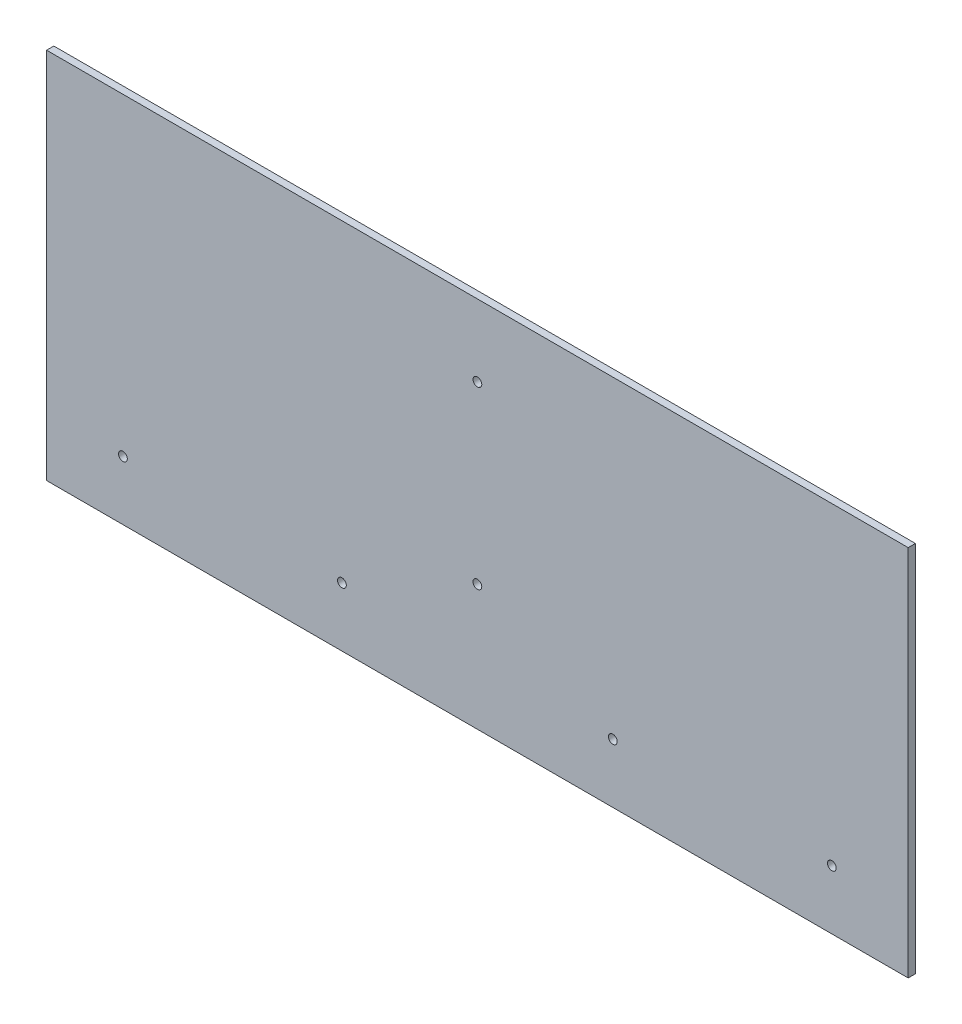
SolidWorks part; units mm, degrees
material "Balsa"
ref_plane "Front Plane" through (0, 0, 0) normal (0, 0, 1) x (1, 0, 0)
ref_plane "Top Plane" through (0, 0, 0) normal (0, 1, 0) x (1, 0, 0)
ref_plane "Right Plane" through (0, 0, 0) normal (1, 0, 0) x (0, 0, -1)
sketch "Sketch1" plane through (0, 0, 0) normal (0, 0, 1) x (1, 0, 0)
  line L1 (223.7, -24.5) -> (-169.7, -24.5)
  line L2 (223.7, -24.5) -> (223.7, 145.6824)
  line L3 (223.7, 145.6824) -> (-169.7, 145.6824)
  line L4 (-169.7, -24.5) -> (-169.7, 145.6824)
  line L5 (223.7, -24.5) -> (-169.7, 145.6824) construction
  line L6 (223.7, 145.6824) -> (-169.7, -24.5) construction
  line L7 (227, -24.5) -> (223.7, -24.5) construction
  line L9 (223.7, 145.6824) -> (54, 145.6824) construction
  line L10 (223.7, 144.1231) -> (223.7, -24.5) construction
  line L11 (-169.7, -24.5) -> (-169.7, 144.1269) construction
  point P4 (27, 60.5912)
extrude "Boss-Extrude1" add sketch "Sketch1" along normal up to surface (3.3 mm away)
sketch "Sketch2" plane through (0, 0, 0) normal (0, 0, -1) x (-1, 0, 0)
  line L0 (-223.7, 145.6824) -> (169.7, 145.6824) construction
  line L1 (0, 0) -> (-54, 0)
  line L2 (0, 0) -> (0, 145.6824)
  line L3 (0, 145.6824) -> (-54, 145.6824)
  line L4 (-54, 0) -> (-54, 145.6824)
  line L5 (0, 0) -> (-54, 145.6824) construction
  line L6 (0, 145.6824) -> (-54, 0) construction
  line L7 (-54, 262.7) -> (-54, 0) construction
  line L8 (-27, 0) -> (-27, 145.6824) construction
  line L9 (169.7, 145.6824) -> (169.7, -24.5) construction
  line L10 (-223.7, 29.5) -> (-54, 29.5)
  line L11 (-223.7, 29.5) -> (-223.7, -24.5)
  line L12 (-223.7, -24.5) -> (-54, -24.5)
  line L13 (-54, 29.5) -> (-54, -24.5)
  line L14 (-223.7, 29.5) -> (-54, -24.5) construction
  line L15 (-223.7, -24.5) -> (-54, 29.5) construction
  line L16 (169.7, 29.5) -> (0, 29.5)
  line L17 (169.7, 29.5) -> (169.7, -24.5)
  line L18 (169.7, -24.5) -> (0, -24.5)
  line L19 (0, 29.5) -> (0, -24.5)
  line L20 (169.7, 29.5) -> (0, -24.5) construction
  line L21 (169.7, -24.5) -> (0, 29.5) construction
  line L22 (-223.7, 2.5) -> (169.7, 2.5) construction
  line L23 (-138.85, -24.5) -> (-138.85, 29.5) construction
  circle A0 centre (-27, 32.8412) radius 2
  circle A1 centre (-27, 112.8412) radius 2
  circle A2 centre (-188.85, 2.5) radius 2
  circle A3 centre (-88.85, 2.5) radius 2
  circle A4 centre (34.85, 2.5) radius 2
  circle A5 centre (134.85, 2.5) radius 2
  point P4 (-27, 72.8412)
  point P20 (-138.85, 2.5)
  point P27 (84.85, 2.5)
  dimension "D1" = 4
  dimension "D2" = 4
  dimension "D3" = 40
  dimension "D4" = 40
  dimension "D5" = 4
  dimension "D6" = 50
extrude "Cut-Extrude1" cut sketch "Sketch2" against normal blind 4 contours A1 | A0 | A2 | A3 | A5 | A4
